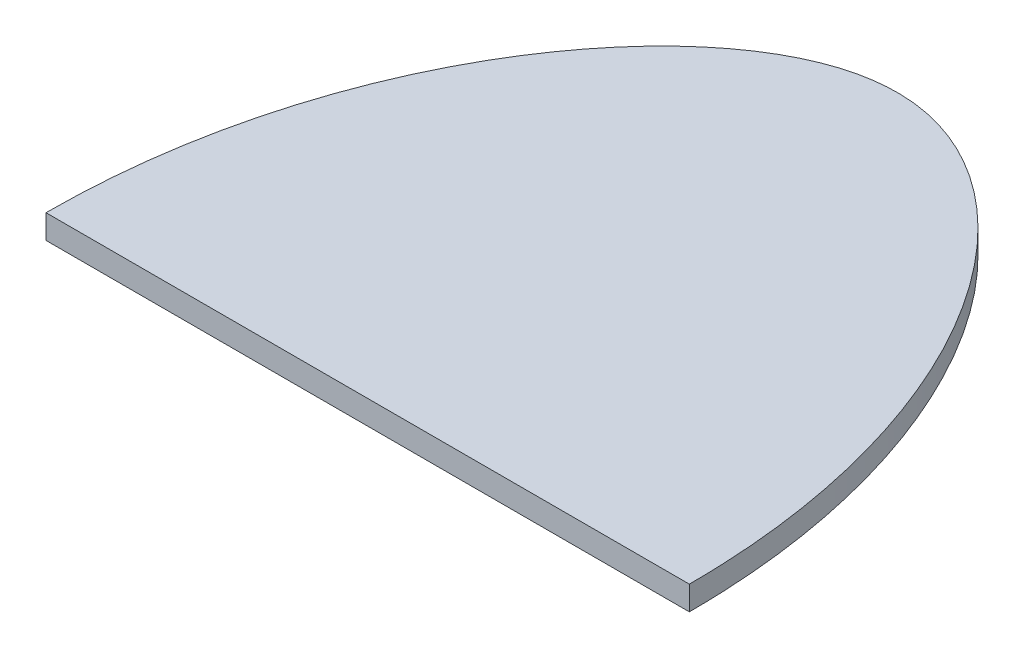
SolidWorks part; units mm, degrees
ref_plane "Front Plane" through (0, 0, 0) normal (0, 0, 1) x (1, 0, 0)
ref_plane "Top Plane" through (0, 0, 0) normal (0, 1, 0) x (1, 0, 0)
ref_plane "Right Plane" through (0, 0, 0) normal (1, 0, 0) x (0, 0, -1)
sketch "Sketch1" plane through (0, 0, 0) normal (0, 1, 0) x (1, 0, 0)
  line L0 (0, 0) -> (85, 0)
  line L1 (42.5, 0) -> (42.5, 70)
  line L2 (70.0314, 70) -> (13.9721, 70) construction
  line L3 (0, 35.1141) -> (0, -35.1141) construction
  line L4 (85, -45.8948) -> (85, 45.8948) construction
  spline S0 degree 3 poles (0, 0) (0, 36) (22.55, 70.2833) (62.45, 70.2833) (85, 36) (85, 0) knots 0 0 0 0 0.45 0.55 1 1 1 1
  dimension "D3" = 120
  dimension "D4" = 120
  dimension "D5" = 120
  dimension "D1" = 85
  dimension "D2" = 70
extrude "Boss-Extrude1" add sketch "Sketch1" along normal blind 3.175 contours S0 L0 L1 | S0 L1 L0 region at (24.627, 0, -29.3598) region at (60.373, 0, -29.3598)
